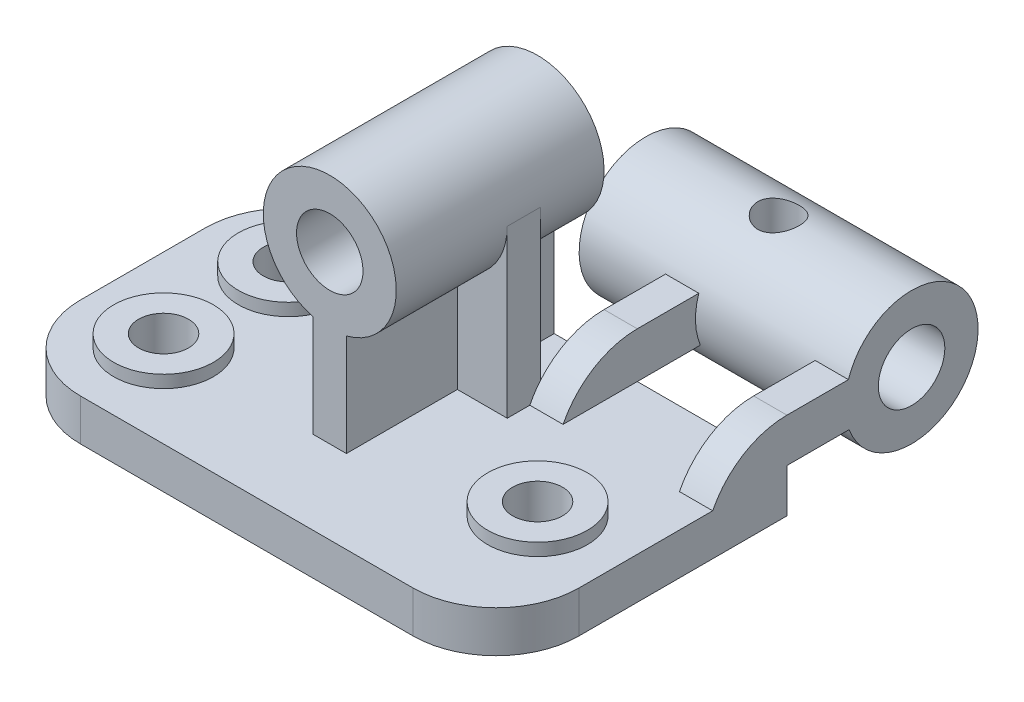
SolidWorks part; units mm, degrees
ref_plane "前视基准面" through (0, 0, 0) normal (0, 0, 1) x (1, 0, 0)
ref_plane "上视基准面" through (0, 0, 0) normal (0, 1, 0) x (1, 0, 0)
ref_plane "右视基准面" through (0, 0, 0) normal (1, 0, 0) x (0, 0, -1)
other "Configuration Table"
sketch "草图3" plane through (0, 0, 0) normal (0, 1, 0) x (1, 0, 0)
  line L0 (-80, 30) -> (-18.5163, 30)
  line L1 (-80, -70) -> (80, -70)
  line L2 (-120, -30) -> (-120, 30)
  line L3 (-80, 70) -> (120, 70)
  line L4 (120, -30) -> (120, 70)
  line L5 (-120, -70) -> (120, 70) construction
  line L6 (-120, 70) -> (120, -70) construction
  line L7 (0, 70) -> (0, -73.3815) construction
  arc A0 (120, -30) -> (80, -70) centre (80, -30) cw
  arc A1 (-120, -30) -> (-80, -70) centre (-80, -30) ccw
  arc A2 (-120, 30) -> (-80, 70) centre (-80, 30) cw
  circle A3 centre (-80, -30) radius 12
  circle A4 centre (-80, 30) radius 12
  circle A6 centre (-80, 30) radius 24
  circle A7 centre (-80, -30) radius 24
  circle A9 centre (80, -10) radius 12
  circle A10 centre (80, -10) radius 24
  point P0 (0, 0)
  dimension "D3" = 40
  dimension "D4" = 24
  dimension "D5" = 48
  dimension "D6" = 60
  dimension "D1" = 240
  dimension "D2" = 140
  dimension "D7" = 160
extrude "凸台-拉伸2" add sketch "草图3" along normal blind 20 contours A6 A4 | A10 A9 | A7 A3 | A2 L2 A1 L1 A0 L4 L3 A10 A7 A6 region at (-103.3212, 0, -30) region at (6.7388, 0, -1.4393) region at (-103.3212, 0, 30) region at (56.6788, 0, 10)
extrude "凸台-拉伸3" add sketch "草图3<7>" along normal blind 26 contours A6 A4 | A7 A3 | A10 A9 region at (-103.3212, 0, -30) region at (-103.3212, 0, 30) region at (56.6788, 0, 10)
sketch "草图3<7>" plane through (0, 0, 0) normal (0, 1, 0) x (1, 0, 0) same geometry as "草图3"
sketch "草图10" plane through (0, 0, -70) normal (0, 0, -1) x (-1, 0, 0)
  line L0 (0, 0) -> (0, 100)
  circle A0 centre (0, 100) radius 16
  circle A1 centre (0, 100) radius 32
  dimension "D2" = 32
  dimension "D3" = 64
  dimension "D1" = 100
extrude "凸台-拉伸5" add sketch "草图10" against normal blind 100 separate body contours A1 A0 region at (21.9874, 121.9874, -70)
sketch "草图15" plane through (0, 20, 0) normal (0, 1, 0) x (1, 0, 0)
  line L0 (0, -30) -> (0, 38) construction
  line L1 (-80, 30) -> (0, 30) construction
  line L2 (32, 38) -> (-32, 38)
  line L3 (-80, 70) -> (120, 70) construction
  line L4 (-8, 70) -> (8, 70)
  line L5 (-32, 38) -> (-32, 22)
  line L6 (0, 38) -> (0, 22)
  line L7 (-8, -30) -> (8, -30)
  line L8 (8, 70) -> (8, -30)
  line L9 (-120, 30) -> (-120, -30)
  line L10 (-80, -70) -> (80, -70)
  line L11 (120, -30) -> (120, 70)
  line L12 (120, 70) -> (-80, 70)
  line L13 (-120, 30) -> (-120, -30)
  line L14 (-80, -70) -> (80, -70)
  line L15 (120, -30) -> (120, 70)
  line L16 (120, 70) -> (-80, 70)
  line L17 (-8, 70) -> (-8, -30)
  line L18 (32, 22) -> (-32, 22)
  line L19 (32, 38) -> (32, 22)
  arc A3 (-80, 70) -> (-120, 30) centre (-80, 30) ccw
  arc A4 (-120, -30) -> (-80, -70) centre (-80, -30) ccw
  arc A5 (80, -70) -> (120, -30) centre (80, -30) ccw
  arc A6 (-80, 70) -> (-120, 30) centre (-80, 30) ccw
  arc A7 (-120, -30) -> (-80, -70) centre (-80, -30) ccw
  arc A8 (80, -70) -> (120, -30) centre (80, -30) ccw
  point P23 (-32, 30)
  dimension "D1" = 0
  dimension "D2" = 32
  dimension "D3" = 16
  dimension "D4" = 8
  dimension "D5" = 80
extrude "凸台-拉伸6" add sketch "草图15" along direction (0, 1, 0) on the side of the normal up to surface (49.0161 mm away) contours L17 L7 L8 L4 up to face at (-32, 100, 30)
sketch "草图16" plane through (0, 20, 0) normal (0, 1, 0) x (1, 0, 0)
  line L0 (0, -70) -> (0, 71.0047) construction
  line L1 (-80, -70) -> (80, -70) construction
  line L2 (-82.3161, 31.4093) -> (0, 31.4093) construction
  line L3 (32, 39.4093) -> (-32, 39.4093)
  line L4 (-32, 39.4093) -> (-32, 31.4093)
  line L5 (0, 39.4093) -> (0, 31.4093)
  line L6 (0, 39.4093) -> (0, 31.4093)
  line L7 (0, 23.4093) -> (0, 31.4093)
  line L8 (-32, 23.4093) -> (-32, 31.4093)
  line L9 (0, 23.4093) -> (-32, 23.4093)
  line L10 (0, 23.4093) -> (0, 31.4093)
  line L11 (0, 23.4093) -> (32, 23.4093)
  line L12 (32, 23.4093) -> (32, 31.4093)
  line L13 (32, 39.4093) -> (32, 31.4093)
  line L15 (120, 70) -> (8, 70)
  line L16 (8, 70) -> (8, -30)
  line L17 (8, -30) -> (-8, -30)
  line L18 (-8, -30) -> (-8, 70)
  line L19 (-8, 70) -> (-80, 70)
  line L20 (-120, 30) -> (-120, -30)
  line L21 (-80, -70) -> (80, -70)
  line L22 (120, -30) -> (120, 70)
  line L23 (120, 70) -> (8, 70)
  line L24 (8, 70) -> (8, -30)
  line L25 (8, -30) -> (-8, -30)
  line L26 (-8, -30) -> (-8, 70)
  line L27 (-8, 70) -> (-80, 70)
  line L28 (-120, 30) -> (-120, -30)
  line L29 (-80, -70) -> (80, -70)
  line L30 (120, -30) -> (120, 70)
  arc A3 (-80, 70) -> (-120, 30) centre (-80, 30) ccw
  arc A4 (-120, -30) -> (-80, -70) centre (-80, -30) ccw
  arc A5 (80, -70) -> (120, -30) centre (80, -30) ccw
  arc A6 (-80, 70) -> (-120, 30) centre (-80, 30) ccw
  arc A7 (-120, -30) -> (-80, -70) centre (-80, -30) ccw
  arc A8 (80, -70) -> (120, -30) centre (80, -30) ccw
  line M34 (8, 70) -> (8, -30)
  line M36 (-8, -30) -> (-8, 70)
  dimension "D1" = 80
  dimension "D3" = 32
  dimension "D4" = 8
  dimension "D2" = 0
extrude "凸台-拉伸9" add sketch "草图16" along direction (0, 1, 0) on the side of the normal up to surface (49.0161 mm away) contours L13 L3 L11 L12 M34 | L9 L3 L4 L8 M36 region at (20, 20, -31.4093) region at (-20, 20, -31.4093) up to face at (0, 100.5081, -20)
sketch3d "3D草图2"
  point P0 (120, 6.0223, -5.9795)
ref_plane "基准面2" through (120, 0, 0) normal (1, 0, 0) x (0, 0, -1)
sketch "草图25" plane through (120, 0, 0) normal (1, 0, 0) x (0, 0, -1)
  circle A0 centre (130.0044, 32) radius 32
  circle A1 centre (130.0044, 32) radius 32
  circle A2 centre (130.0044, 32) radius 16
  dimension "D3" = 64
  dimension "D4" = 32
  dimension "D1" = 32
  dimension "D2" = 60.0044
extrude "凸台-拉伸10" add sketch "草图25" against normal blind 128 separate body contours A0 A2 region at (120, 32, -98.9095)
sketch "草图28" plane through (0, 20, 0) normal (0, 1, 0) x (1, 0, 0)
  line L0 (120, 69.7023) -> (56, 70)
  line L3 (120, -55.6452) -> (120, 55.6452) construction
  line L4 (8, 70) -> (120, 70) construction
  line L5 (56, 70) -> (56, 130.0044)
  circle A0 centre (56, 130.0044) radius 10
  dimension "D2" = 20
  dimension "D1" = 64
extrude "切除-拉伸1" cut sketch "草图28" against normal through all both and the other way through all contours A0
sketch "草图30" plane through (120, 0, 0) normal (1, 0, 0) x (0, 0, -1)
  line L0 (70, 0) -> (70, 2)
  line L1 (-30, 20) -> (70, 20) construction
  line L2 (70, 42) -> (70, 20)
  line L3 (70, 20) -> (34.2789, 20)
  arc A0 (70, 42) -> (34.2789, 20) centre (70, 2) ccw
  dimension "D1" = 2
extrude "凸台-拉伸11" add sketch "草图30" against normal blind 16 contours L2 L3 A0
sketch "草图31" plane through (0, 20, 0) normal (0, 1, 0) x (1, 0, 0)
  line L0 (104, 70) -> (48, 70) construction
  line L1 (8, 70) -> (104, 70) construction
  line L2 (76, 89.2956) -> (76, 40.6018) construction
ref_plane "基准面3" through (48, 0, 0) normal (1, 0, 0) x (0, 0, -1)
sketch "草图34" plane through (48, 0, 0) normal (1, 0, 0) x (0, 0, -1)
  line L0 (70, 0) -> (70, 2)
  line L1 (70, 42) -> (70, 0) construction
  line L2 (39.4093, 20) -> (23.4093, 20) construction
  line L3 (-30, 20) -> (34.2789, 20) construction
  line L4 (70, 69.0161) -> (70, 20) construction
  line L5 (34.2789, 20) -> (70, 20)
  line L6 (70, 20) -> (70, 42)
  arc A0 (34.2789, 20) -> (70, 42) centre (70, 2) cw
  dimension "D2" = 40
  dimension "D1" = 2
extrude "凸台-拉伸12" add sketch "草图34" against normal blind 16 contours A0 L5 L6 region at (48, 29.0473, -55.9269)
sketch "草图37" plane through (0, 0, -70) normal (0, 0, -1) x (-1, 0, 0)
  line L0 (-104, 20) -> (-120, 21)
  line L1 (-120, 42) -> (-120, 0) construction
  line L2 (-120, 21) -> (-120, 42)
  line L3 (-120, 42) -> (-104, 42)
  line L4 (-104, 42) -> (-104, 20)
extrude "凸台-拉伸13" add sketch "草图37" along normal up to surface (29.607 mm away) up to face at (65.8422, 63.951, -131.7738)
sketch "草图38" plane through (0, 0, -70) normal (0, 0, -1) x (-1, 0, 0)
  line L1 (-48, 20) -> (-32, 20)
  line L2 (-32, 20) -> (-32, 42)
  line L3 (-32, 42) -> (-48, 42)
  line L4 (-48, 42) -> (-48, 20)
extrude "凸台-拉伸14" add sketch "草图38" along normal up to surface (30.3396 mm away) up to face at (111.9936, 31.4907, -114.943)
